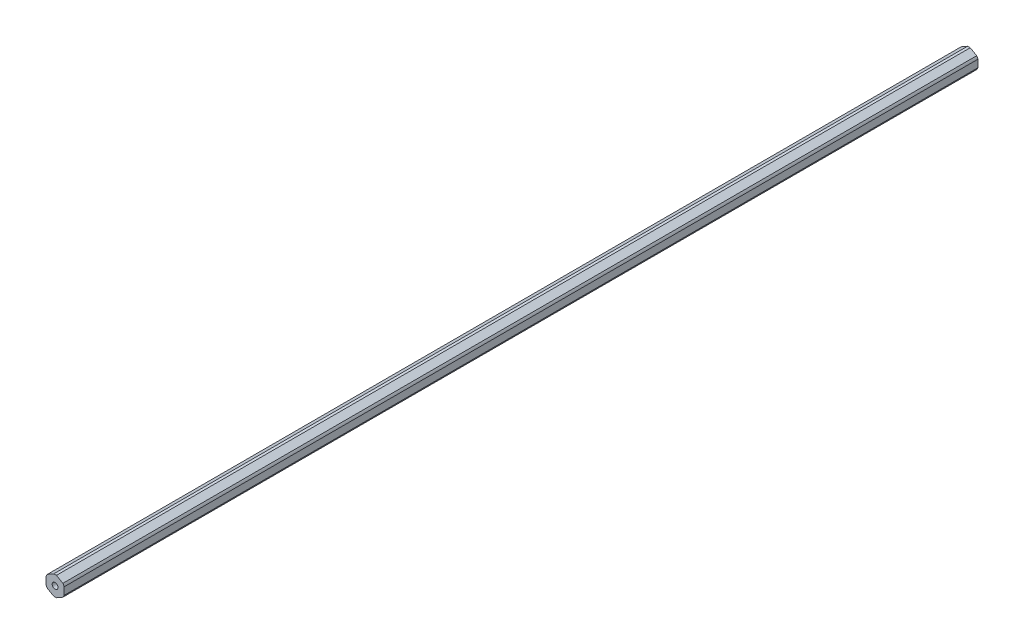
SolidWorks part; units mm, degrees
ref_plane "Front Plane" through (0, 0, 0) normal (0, 0, 1) x (1, 0, 0)
ref_plane "Top Plane" through (0, 0, 0) normal (0, 1, 0) x (1, 0, 0)
ref_plane "Right Plane" through (0, 0, 0) normal (1, 0, 0) x (0, 0, -1)
sketch "Sketch1" plane through (0, 0, 0) normal (0, 0, 1) x (1, 0, 0)
  line L1 (0, 7.3323) -> (-6.35, 3.6662)
  line L2 (-6.35, 3.6662) -> (-6.35, -3.6662)
  line L3 (-6.35, -3.6662) -> (0, -7.3323)
  line L4 (0, -7.3323) -> (6.35, -3.6662)
  line L5 (6.35, -3.6662) -> (6.35, 3.6662)
  line L6 (6.35, 3.6662) -> (0, 7.3323)
  circle A0 centre (0, 0) radius 6.35 construction
  circle A1 centre (0, 0) radius 6.858
  dimension "D1" = 12.7
  dimension "D2" = 13.716
extrude "Boss-Extrude1" add sketch "Sketch1" along normal mid plane 638.175 contours L5 A1 L6 L1 L2 L3 L4 region at (0, 0, 0)
hole_wizard "#10-32 Tapped Hole1" positions "3DSketch1" profile "Sketch2" tap size "#10-32" standard "ANSI Inch"
sketch3d "3DSketch1"
  line L0 (0, 0, 319.0875) -> (0, 0, -319.0875) construction
  line L1 (0, 0, 319.0875) -> (0, 0, -319.0875) construction
  point P0 (0, 0, 319.0875)
  point P4 (0, 0, -319.0875)
sketch "Sketch2" plane through (0, 0, 319.0875) normal (1, 0, 0) x (0, -1, 0)
  line L0 (0, 0) -> (0, 13.1513)
  line L1 (0, 13.1513) -> (2.0193, 11.938)
  line L2 (2.0193, 11.938) -> (2.0193, 0)
  line L5 (2.0193, 0) -> (0, 0)
  line L10 (0, 13.1513) -> (-2.0193, 11.938) construction
  line L11 (0, -6.35) -> (0, 107.95) construction
  dimension "Tap Drill Dia." = 4.0386
  dimension "Tap Drill Depth" = 11.938
  dimension "Drill Angle" = 118
cosmetic thread "Hole Thread1" parameters "D1"=9.652, "D2"=4.826
cosmetic thread "Hole Thread2" parameters "D1"=9.652, "D2"=4.826
